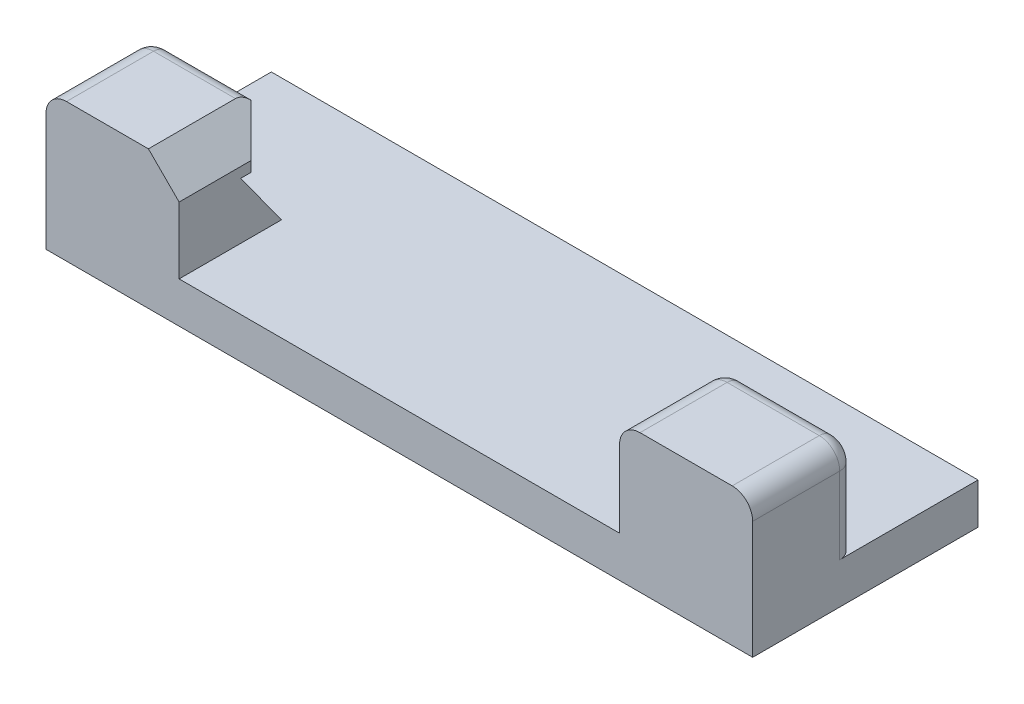
SolidWorks part; units mm, degrees
ref_plane "Front Plane" through (0, 0, 0) normal (0, 0, 1) x (1, 0, 0)
ref_plane "Top Plane" through (0, 0, 0) normal (0, 1, 0) x (1, 0, 0)
ref_plane "Right Plane" through (0, 0, 0) normal (1, 0, 0) x (0, 0, -1)
sketch "Sketch1" plane through (0, 0, 0) normal (0, 1, 0) x (1, 0, 0)
  line L1 (34.5, 11) -> (-34.5, 11)
  line L2 (34.5, 11) -> (34.5, -11)
  line L3 (34.5, -11) -> (-34.5, -11)
  line L4 (-34.5, 11) -> (-34.5, -11)
  line L5 (34.5, 11) -> (-34.5, -11) construction
  line L6 (34.5, -11) -> (-34.5, 11) construction
  point P0 (0, 0)
  dimension "D1" = 69
  dimension "D2" = 22
extrude "Boss-Extrude1" add sketch "Sketch1" along normal blind 3 and the other way blind 1
sketch "Sketch2" plane through (0, 3, 0) normal (0, 1, 0) x (1, 0, 0)
  line L1 (-34.5, -11) -> (-21.5, -11)
  line L2 (-34.5, -11) -> (-34.5, -1)
  line L3 (-34.5, -1) -> (-21.5, -1)
  line L4 (-21.5, -11) -> (-21.5, -1)
  line L5 (34.5, -11) -> (21.5, -11)
  line L6 (34.5, -11) -> (34.5, -1)
  line L7 (34.5, -1) -> (21.5, -1)
  line L8 (21.5, -11) -> (21.5, -1)
  dimension "D1" = 13
  dimension "D2" = 10
  dimension "D3" = 13
  dimension "D4" = 10
extrude "Boss-Extrude2" add sketch "Sketch2" along normal blind 9.5
sketch "Sketch3" plane through (-21.5, 0, 0) normal (1, 0, 0) x (0, 0, -1)
  line L0 (-11, 12.5) -> (-1, 12.5) construction
  line L2 (-1, 3) -> (-1, 8.5)
  line L3 (-1, 8.5) -> (-5, 8.5)
  line L6 (-1, 3) -> (-5, 8.5)
  dimension "D1" = 4
  dimension "D2" = 4
extrude "Cut-Extrude1" cut sketch "Sketch3" against normal blind 10
fillet "Fillet1" radius 2 2 edges at (21.5, 12.5, 6) (34.5, 12.5, 6)
fillet "Fillet2" radius 1.5 5 edges at (34.5, 6.75, 1) (33.9142, 11.9142, 1) (21.5, 6.75, 1) (22.0858, 11.9142, 1) (28, 12.5, 1)
chamfer "Chamfer1" distance 3 angle 45 2 edges at (-21.5, 10.5, 1) (-21.5, 12.5, 6)
fillet "Fillet3" radius 1.5 2 edges at (-34.5, 7.75, 1) (-29.5, 12.5, 1)
fillet "Fillet4" radius 2 2 edges at (-34.0607, 12.0607, 1.4393) (-34.5, 12.5, 6.75)
